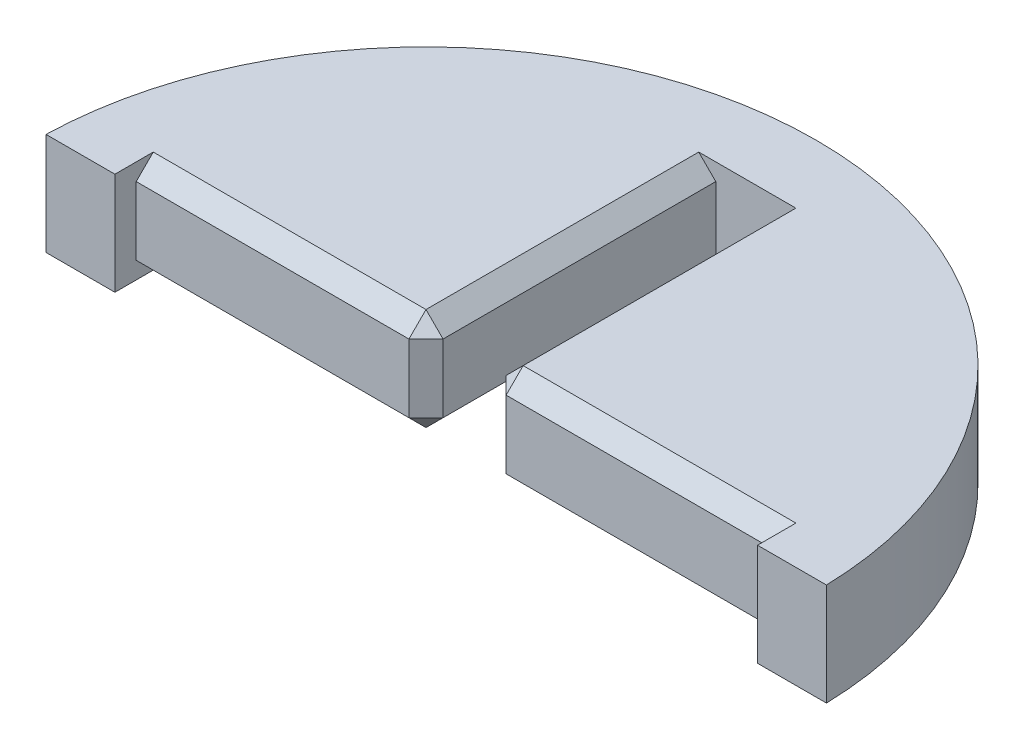
SolidWorks part; units mm, degrees
ref_plane "Front Plane" through (0, 0, 0) normal (0, 0, 1) x (1, 0, 0)
ref_plane "Top Plane" through (0, 0, 0) normal (0, 1, 0) x (1, 0, 0)
ref_plane "Right Plane" through (0, 0, 0) normal (1, 0, 0) x (0, 0, -1)
sketch "Sketch2" plane through (0, 0, 0) normal (0, 1, 0) x (1, 0, 0)
  line L0 (0, 0) -> (-9.125, 0) construction
  line L1 (-9.125, 0) -> (-9.125, 0.625) construction
  line L2 (-9.125, 0.625) -> (-0.625, 0.625) construction
  line L3 (-0.625, 0.625) -> (-0.625, 9.125) construction
  line L4 (-0.625, 9.125) -> (0, 9.125) construction
  line L5 (0, 9.125) -> (0.625, 9.125) construction
  line L6 (0.625, 9.125) -> (0.625, 0.625) construction
  line L7 (0.625, 0.625) -> (9.125, 0.625) construction
  line L8 (9.125, 0.625) -> (9.125, 0) construction
  line L9 (9.125, 0) -> (0, 0) construction
  line L10 (0, 9.125) -> (0, 0) construction
  line L11 (-9.425, 0.3) -> (-9.425, 0.925)
  line L12 (-9.425, 0.925) -> (-0.925, 0.925)
  line L13 (-0.925, 0.925) -> (-0.925, 9.425)
  line L14 (-0.925, 9.425) -> (0, 9.425)
  line L15 (0, 9.425) -> (0.925, 9.425)
  line L16 (0.925, 9.425) -> (0.925, 0.925)
  line L17 (0.925, 0.925) -> (9.425, 0.925)
  line L18 (9.425, 0.925) -> (9.425, 0.3)
  line L21 (-11.4462, 0.3) -> (-11.7462, 0.3) construction
  line L22 (-9.425, 0) -> (-9.425, 0.925) construction
  line L23 (-9.425, 0.3) -> (-11.4462, 0.3)
  line L24 (9.425, 0.925) -> (9.425, 0) construction
  line L25 (-9.425, 0.3) -> (9.425, 0.3) construction
  line L26 (9.425, 0.3) -> (11.4462, 0.3)
  arc A0 (-11.4462, 0.3) -> (11.4462, 0.3) centre (0, 0) cw
  circle A3 centre (0, 0) radius 11.75 construction
  dimension "D1" = 1.25
  dimension "D2" = 18.25
  dimension "D4" = 0.3
  dimension "D5" = 0.3
  dimension "D3" = 0.3
extrude "Boss-Extrude1" add sketch "Sketch2" along normal up to surface (3 mm away)
chamfer "Chamfer1" distance 0.5 angle 45 10 edges at (5.175, 0, -0.925) (0.925, 0, -5.175) (0.925, 1.5, -0.925) (5.175, 3, -0.925) (0.925, 3, -5.175) (-5.175, 0, -0.925) (-0.925, 0, -5.175) (-0.925, 1.5, -0.925) (-0.925, 3, -5.175) (-5.175, 3, -0.925)
equation "\"Tolerance\"=0.3"
equation "\"D3@Sketch2\"=\"Tolerance\""
equation "\"D4@Sketch2\"=\"Tolerance\""
equation "\"D5@Sketch2\"=\"Tolerance\""
